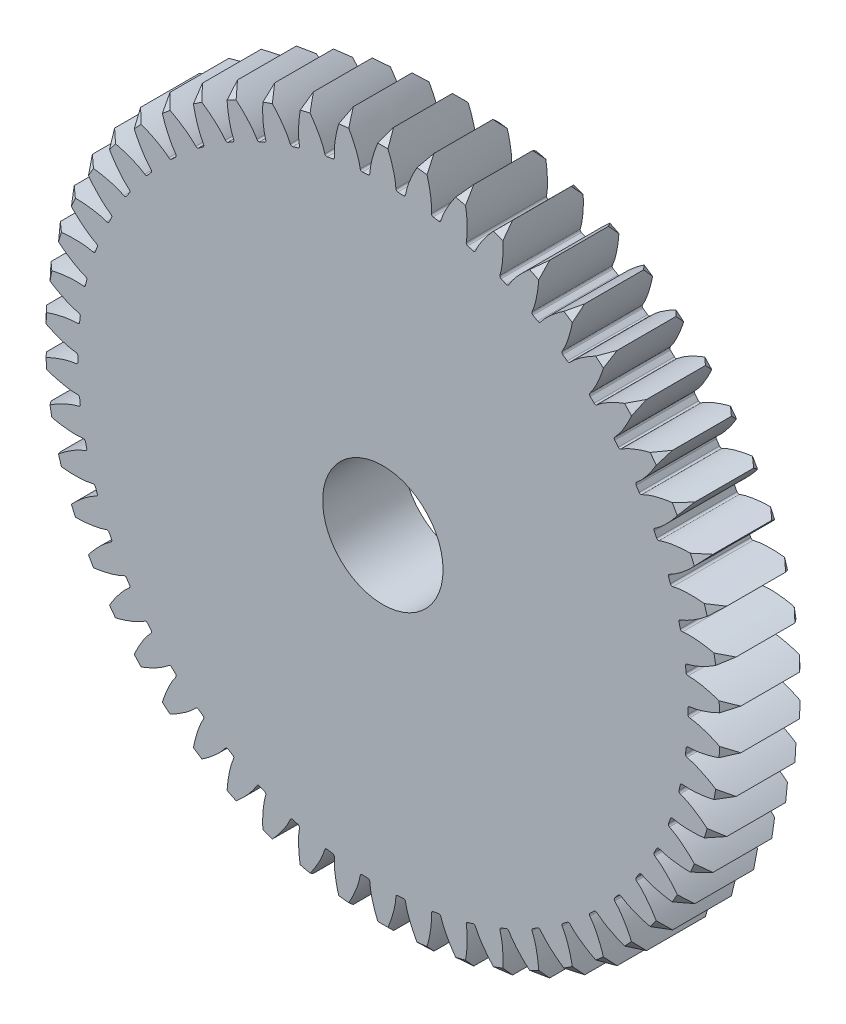
SolidWorks part; units mm, degrees
ref_plane "Piano frontale" through (0, 0, 0) normal (0, 0, 1) x (1, 0, 0)
ref_plane "Piano superiore" through (0, 0, 0) normal (0, 1, 0) x (1, 0, 0)
ref_plane "Piano destro" through (0, 0, 0) normal (1, 0, 0) x (0, 0, -1)
sketch "Schizzo1" plane through (0, 0, 0) normal (0, 0, 1) x (1, 0, 0)
  circle A0 centre (0, 0) radius 15
  circle A1 centre (0, 0) radius 87
  dimension "D1" = 30
  dimension "D2" = 174
extrude "Estrusione-Estrusione1" add sketch "Schizzo1" along normal blind 20
sketch "Schizzo2" plane through (0, 0, 20) normal (0, 0, 1) x (1, 0, 0)
  line L0 (0, 0) -> (75.991, 1.1673)
  line L1 (0, 0) -> (75.991, -1.1673)
  line L2 (0, 0) -> (76, 0) construction
  arc A0 (75.991, -1.1673) -> (75.991, 1.1673) centre (0, 0) ccw
  arc A1 (80.9659, -2.35) -> (80.9659, 2.35) centre (0, 0) ccw
  arc A2 (89.7178, -7.1218) -> (89.7178, 7.1218) centre (0, 0) ccw
  spline S0 degree 4 poles (75.991, 1.1673) (76.0633, 1.1684) (76.2077, 1.1737) (76.4959, 1.1968) (76.9262, 1.2504) (77.4252, 1.3331) (78.1054, 1.4731) (78.8922, 1.6692) (79.7815, 1.9314) (80.7689, 2.2688) (81.842, 2.6817) (82.9959, 3.1785) (84.5565, 3.9256) (86.2711, 4.8627) (88.0346, 5.9484) (90.2362, 7.4615) (92.5896, 9.2718) (95.2377, 11.5867) (99.4273, 15.7968) (104.381, 21.9394) (109.5204, 30.2599) (114.2165, 40.9226) (117.557, 52.078) (119.6161, 63.5353) (120.5079, 75.7161) (120.0341, 90.8334) (117.6246, 105.7901) (113.4698, 120.3435) (106.9386, 136.5194) (100.1488, 149.3929) (92.1555, 161.5503) (81.2803, 175.1847) (71.2345, 185.7061) (60.3304, 195.3309) (49.8486, 203.1524) (42.6104, 208.0089) (35.1881, 212.5757) (27.5921, 216.8508) (18.4997, 221.4094) (7.832, 226.0266) (-1.7105, 229.546) (-10.0155, 232.1906) (-17.0092, 234.1468) (-22.6435, 235.5635) (-28.3129, 236.8322) (-34.0133, 237.9534) (-39.0248, 238.8058) (-43.3346, 239.4451) (-46.9346, 239.917) (-49.8189, 240.2582) (-52.7078, 240.5631) (-55.5993, 240.8318) (-58.4957, 241.0645) (-61.3916, 241.2612) (-64.0363, 241.4078) (-66.4145, 241.5141) (-68.316, 241.5809) (-69.6999, 241.6208) (-70.8965, 241.6485) (-71.7671, 241.666) (-72.906, 241.6832) (-73.7248, 241.6924) (-75.0501, 241.7024) (-76.1034, 241.7032) (-77.6296, 241.6995) (-79.3505, 241.6823) (-81.4236, 241.6464) (-83.7549, 241.5821) (-86.6892, 241.4737) (-90.1967, 241.2982) (-93.7084, 241.0666) (-97.2109, 240.7791) (-100.1289, 240.5025) (-102.4597, 240.2591) (-104.7891, 239.9937) (-107.1152, 239.7064) (-108.8581, 239.4745) (-110.0188, 239.3126) (-110.599, 239.2299) knots 0 0 0 0 0 0.000701 0.001401 0.002802 0.004203 0.005604 0.008133 0.010661 0.01319 0.015718 0.019279 0.022839 0.02996 0.034653 0.039347 0.048734 0.05873 0.068727 0.096889 0.125051 0.153212 0.181374 0.209535 0.237696 0.271429 0.327752 0.355914 0.384075 0.440398 0.46856 0.496721 0.553044 0.581206 0.609367 0.623448 0.637529 0.66569 0.693852 0.722013 0.750174 0.764255 0.778336 0.792417 0.806497 0.820578 0.834659 0.841699 0.84874 0.85578 0.86282 0.869861 0.876901 0.883942 0.890982 0.895509 0.900036 0.9023 0.904564 0.906827 0.909091 0.911932 0.914773 0.917614 0.920455 0.926136 0.931818 0.9375 0.943182 0.954545 0.965909 0.971591 0.977273 0.982955 0.988636 0.994318 1 1 1 1 1 construction
  spline S1 degree 4 poles (75.991, 1.1673) (76.0633, 1.1684) (76.2077, 1.1737) (76.4959, 1.1968) (76.9262, 1.2504) (77.4252, 1.3331) (78.1054, 1.4731) (78.8922, 1.6692) (79.7815, 1.9314) (80.7689, 2.2688) (81.842, 2.6817) (82.9959, 3.1785) (84.5565, 3.9256) (86.2711, 4.8627) (87.7996, 5.8037) (88.9821, 6.6023) (89.5482, 7.0009) (89.7178, 7.1218) knots 0 0 0 0 0 0.000701 0.001401 0.002802 0.004203 0.005604 0.008133 0.010661 0.01319 0.015718 0.019279 0.022839 0.02996 0.034653 0.036672 0.036672 0.036672 0.036672 0.036672
  spline S2 degree 4 poles (75.991, -1.1673) (76.0633, -1.1684) (76.2077, -1.1737) (76.4959, -1.1968) (76.9262, -1.2504) (77.4252, -1.3331) (78.1054, -1.4731) (78.8922, -1.6692) (79.7815, -1.9314) (80.7689, -2.2688) (81.842, -2.6817) (82.9959, -3.1785) (84.5565, -3.9256) (86.2711, -4.8627) (88.0346, -5.9484) (90.2362, -7.4615) (92.5896, -9.2718) (95.2377, -11.5867) (99.4273, -15.7968) (104.381, -21.9394) (109.5204, -30.2599) (114.2165, -40.9226) (117.557, -52.078) (119.6161, -63.5353) (120.5079, -75.7161) (120.0341, -90.8334) (117.6246, -105.7901) (113.4698, -120.3435) (106.9386, -136.5194) (100.1488, -149.3929) (92.1555, -161.5503) (81.2803, -175.1847) (71.2345, -185.7061) (60.3304, -195.3309) (49.8486, -203.1524) (42.6104, -208.0089) (35.1881, -212.5757) (27.5921, -216.8508) (18.4997, -221.4094) (7.832, -226.0266) (-1.7105, -229.546) (-10.0155, -232.1906) (-17.0092, -234.1468) (-22.6435, -235.5635) (-28.3129, -236.8322) (-34.0133, -237.9534) (-39.0248, -238.8058) (-43.3346, -239.4451) (-46.9346, -239.917) (-49.8189, -240.2582) (-52.7078, -240.5631) (-55.5993, -240.8318) (-58.4957, -241.0645) (-61.3916, -241.2612) (-64.0363, -241.4078) (-66.4145, -241.5141) (-68.316, -241.5809) (-69.6999, -241.6208) (-70.8965, -241.6485) (-71.7671, -241.666) (-72.906, -241.6832) (-73.7248, -241.6924) (-75.0501, -241.7024) (-76.1034, -241.7032) (-77.6296, -241.6995) (-79.3505, -241.6823) (-81.4236, -241.6464) (-83.7549, -241.5821) (-86.6892, -241.4737) (-90.1967, -241.2982) (-93.7084, -241.0666) (-97.2109, -240.7791) (-100.1289, -240.5025) (-102.4597, -240.2591) (-104.7891, -239.9937) (-107.1152, -239.7064) (-108.8581, -239.4745) (-110.0188, -239.3126) (-110.599, -239.2299) knots 0 0 0 0 0 0.000701 0.001401 0.002802 0.004203 0.005604 0.008133 0.010661 0.01319 0.015718 0.019279 0.022839 0.02996 0.034653 0.039347 0.048734 0.05873 0.068727 0.096889 0.125051 0.153212 0.181374 0.209535 0.237696 0.271429 0.327752 0.355914 0.384075 0.440398 0.46856 0.496721 0.553044 0.581206 0.609367 0.623448 0.637529 0.66569 0.693852 0.722013 0.750174 0.764255 0.778336 0.792417 0.806497 0.820578 0.834659 0.841699 0.84874 0.85578 0.86282 0.869861 0.876901 0.883942 0.890982 0.895509 0.900036 0.9023 0.904564 0.906827 0.909091 0.911932 0.914773 0.917614 0.920455 0.926136 0.931818 0.9375 0.943182 0.954545 0.965909 0.971591 0.977273 0.982955 0.988636 0.994318 1 1 1 1 1 construction
  spline S3 degree 4 poles (75.991, -1.1673) (76.0633, -1.1684) (76.2077, -1.1737) (76.4959, -1.1968) (76.9262, -1.2504) (77.4252, -1.3331) (78.1054, -1.4731) (78.8922, -1.6692) (79.7815, -1.9314) (80.7689, -2.2688) (81.842, -2.6817) (82.9959, -3.1785) (84.5565, -3.9256) (86.2711, -4.8627) (87.7996, -5.8037) (88.9821, -6.6023) (89.5482, -7.0009) (89.7178, -7.1218) knots 0 0 0 0 0 0.000701 0.001401 0.002802 0.004203 0.005604 0.008133 0.010661 0.01319 0.015718 0.019279 0.022839 0.02996 0.034653 0.036672 0.036672 0.036672 0.036672 0.036672
  circle M4 centre (0, 0) radius 87
  dimension "D1" = 152
  dimension "D2" = 162
  dimension "D3" = 180
  dimension "D4" = 4.7
extrude "Taglio-Estrusione2" cut sketch "Schizzo2" against normal blind 20 contours A0 S3 A1 S1 | A1 S3 S1 M4 | S3 A2 S1 M4 region at (78.8042, 0, 20) region at (84.3612, 0, 20) region at (88.5041, 0, 20)
fillet "Raccordo1" radius 0.5 2 edges at (75.991, -1.1673, 10) (75.991, 1.1673, 10)
chamfer "Smusso1" distance 3 angle 45 2 edges at (-87, 0, 0) (-87, 0, 20)
pattern_circular "RipetizioneCircolare1" count 54 over 360 about axis through (0, 0, 20) along (0, 0, -1) of "Taglio-Estrusione2", "Raccordo1" reverse direction yes
